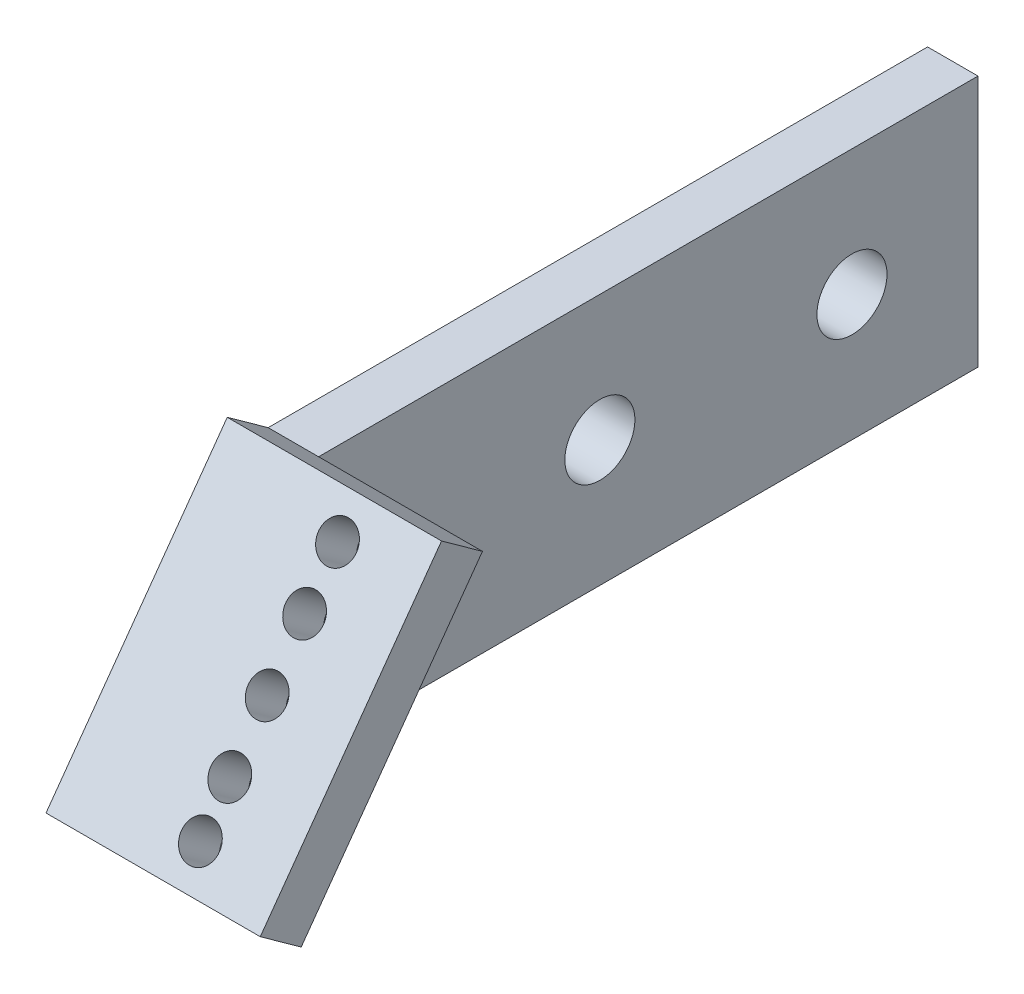
SolidWorks part; units mm, degrees
note: '?' marks a value the reader was unsure of.
ref_plane "Front Plane" through (0, 0, 0) normal (0, 0, 1) x (1, 0, 0)
ref_plane "Top Plane" through (0, 0, 0) normal (0, 1, 0) x (1, 0, 0)
ref_plane "Right Plane" through (0, 0, 0) normal (1, 0, 0) x (0, 0, -1)
sketch "Sketch1" plane through (0, 0, 0) normal (1, 0, 0) x (0, 0, -1)
  line L0 (-10, -10) -> (30, -10) construction
  line L1 (-10, 0) -> (30, 0)
  line L2 (-10, 0) -> (-10, -20)
  line L3 (-10, -20) -> (30, -20)
  line L4 (30, 0) -> (30, -20)
  line L5 (0, 0) -> (0, -10) construction
  circle A0 centre (0, -10) radius 2.78
  circle A1 centre (20, -10) radius 2.78
  dimension "D1" = 5.56
  dimension "D2" = 5.56
  dimension "D3" = 20
  dimension "D4" = 20
  dimension "D5" = 40
  dimension "D6" = 10
  dimension "D7" = 10
extrude "Boss-Extrude1" add sketch "Sketch1" along normal blind 4
ref_plane "Plane1" through (0, -20, 0) normal (0, -1, 0) x (-1, 0, 0)
sketch "Sketch3" plane through (0, -20, 0) normal (0, -1, 0) x (-1, 0, 0)
  line L1 (-4, -10) -> (0, -10)
  line L2 (-4, -10) -> (-4, -24.38)
  line L3 (-4, -24.38) -> (0, -24.38)
  line L4 (0, -10) -> (0, -24.38)
  dimension "D1" = 14.38
ref_plane "Plane2" through (0, 4.7397, 6.5921) normal (0, 0.5838, 0.8119) x (1, 0, 0)
ref_plane "Plane3" through (0, 10.5774, 14.7113) normal (0, 0.5838, 0.8119) x (1, 0, 0)
ref_axis "Axis1" through (52.3068, 0, 22.3165) along (-1, 0, 0)?
ref_axis "Axis2" through (-32.557, -20, 36.6965) along (1, 0, 0)?
ref_axis "Axis3" through (4, -23.3018, 39.0705) along (0, 0.8119, -0.5838)?
ref_axis "Axis4" through (0, 24.0512, 5.0237) along (0, -0.8119, 0.5838)?
sketch "Sketch5" plane through (0, 10.5774, 14.7113) normal (0, 0.5838, 0.8119) x (1, 0, 0)
  line L0 (52.3068, -13.0277) -> (-32.557, -13.0277) construction
  line L1 (0, -13.0277) -> (4, -13.0277)
  line L2 (0, -13.0277) -> (0, -37.6607)
  line L3 (0, -37.6607) -> (4, -37.6607)
  line L4 (4, -13.0277) -> (4, -37.6607)
  line L5 (0, 16.5949) -> (0, -41.7274) construction
  line L6 (4, -41.7274) -> (4, 16.5949) construction
  line L7 (-32.557, -37.6607) -> (52.3068, -37.6607) construction
loft "Loft1" add profiles "Sketch5" section "Sketch5" section face at (2, -10, 10) connector at (4, 0, 22.3165) connector at (4, 0, 10)
sketch "Sketch6" plane through (0, 10.5774, 14.7113) normal (0, 0.5838, 0.8119) x (1, 0, 0)
  line L0 (52.3068, -13.0277) -> (-32.557, -13.0277) construction
  line L1 (0, -13.0277) -> (17, -13.0277)
  line L2 (0, -13.0277) -> (0, -37.6607)
  line L3 (0, -37.6607) -> (17, -37.6607)
  line L4 (17, -13.0277) -> (17, -37.6607)
  line L5 (-32.557, -37.6607) -> (52.3068, -37.6607) construction
  line L6 (4, -13.0277) -> (17, -37.6607) construction
  line L8 (17, -13.0277) -> (4, -37.6607) construction
  line L9 (10.5, -13.0277) -> (10.5, -37.6607) construction
  line L10 (0, 16.5949) -> (0, -41.7274) construction
  circle A0 centre (10.5, -20.5007) radius 1.5
  circle A1 centre (10.5, -25.5807) radius 1.5
  circle A2 centre (10.5, -30.6607) radius 1.5
  circle A3 centre (10.5, -34.6607) radius 1.5
  circle A4 centre (10.5, -16.0277) radius 1.5
  point P20 (12.75, -12.2236)
  point P23 (4, -37.6607)
  point P27 (4, -13.0277)
  dimension "D3" = 3
  dimension "D4" = 3
  dimension "D5" = 3
  dimension "D9" = 3
  dimension "D2" = 3
  dimension "D1" = 17
  dimension "D6" = 5.08
  dimension "D7" = 5.08
  dimension "D8" = 7
  dimension "D10" = 3
  dimension "D11" = 3
  dimension "D12" = 4.473
  dimension "D13" = 4
extrude "Boss-Extrude2" add sketch "Sketch6" along normal blind 4
